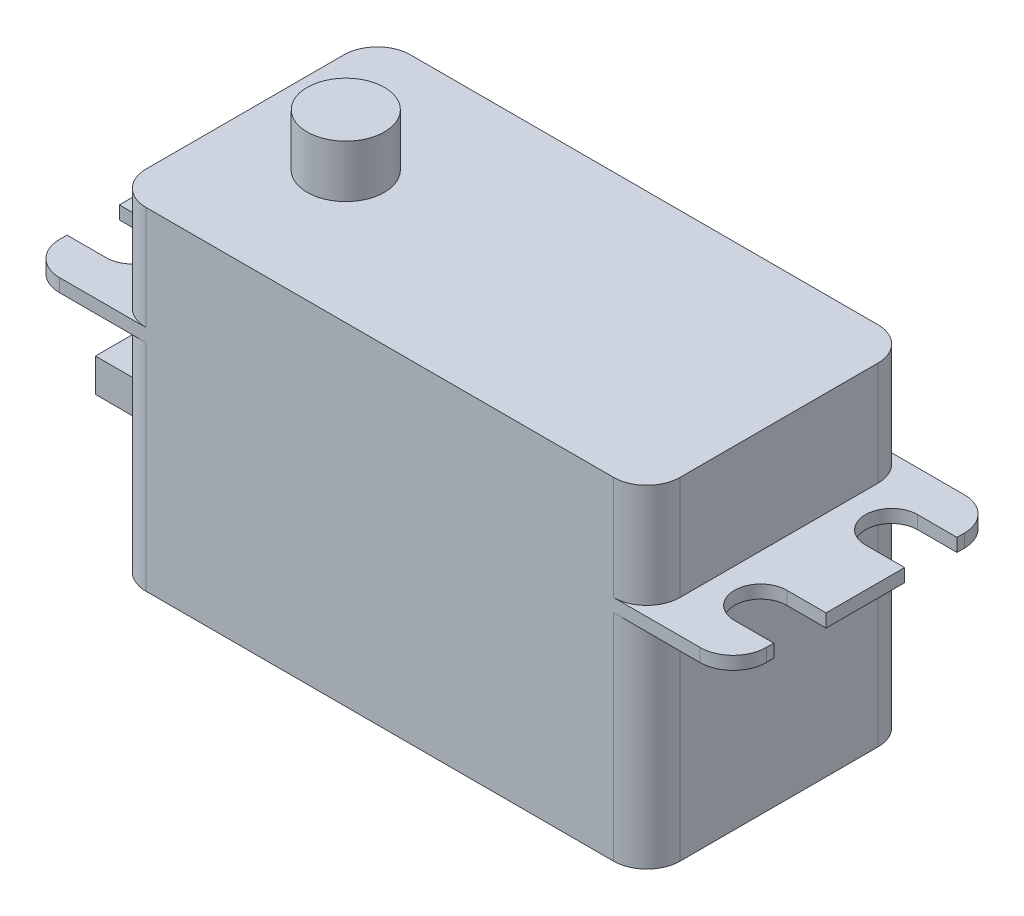
SolidWorks part; units mm, degrees
ref_plane "Front Plane" through (0, 0, 0) normal (0, 0, 1) x (1, 0, 0)
ref_plane "Top Plane" through (0, 0, 0) normal (0, 1, 0) x (1, 0, 0)
ref_plane "Right Plane" through (0, 0, 0) normal (1, 0, 0) x (0, 0, -1)
sketch "Sketch1" plane through (0, 0, 0) normal (0, 1, 0) x (1, 0, 0)
  line L0 (-16.17, 0) -> (16.17, 0) construction
  line L1 (-24.46, -10.1) -> (24.46, -10.1)
  line L2 (-27, -7.56) -> (-27, 7.56)
  line L3 (-24.46, 10.1) -> (24.46, 10.1)
  line L4 (27, -7.56) -> (27, 7.56)
  line L5 (-27, -10.1) -> (27, 10.1) construction
  line L6 (-27, 10.1) -> (27, -10.1) construction
  line L7 (0, -11.11) -> (0, 11.11) construction
  line L8 (24, 3) -> (27, 3)
  line L9 (24, 7) -> (27, 7)
  line L10 (27, 7) -> (27, 3)
  line L11 (24, -3) -> (27, -3)
  line L12 (24, -7) -> (27, -7)
  line L13 (27, -7) -> (27, -3)
  line L14 (-24, 7) -> (-27, 7)
  line L15 (-24, 3) -> (-27, 3)
  line L16 (-27, 3) -> (-27, 7)
  line L17 (-24, -7) -> (-27, -7)
  line L18 (-24, -3) -> (-27, -3)
  line L19 (-27, -3) -> (-27, -7)
  arc A0 (24, 7) -> (24, 3) centre (24, 5) ccw
  arc A1 (24, -7) -> (24, -3) centre (24, -5) cw
  arc A2 (-24, -7) -> (-24, -3) centre (-24, -5) ccw
  arc A3 (-24, 7) -> (-24, 3) centre (-24, 5) cw
  arc A4 (-24.46, -10.1) -> (-27, -7.56) centre (-24.46, -7.56) cw
  arc A5 (24.46, -10.1) -> (27, -7.56) centre (24.46, -7.56) ccw
  arc A6 (24.46, 10.1) -> (27, 7.56) centre (24.46, 7.56) cw
  arc A7 (-27, 7.56) -> (-24.46, 10.1) centre (-24.46, 7.56) cw
  point P0 (0, 0)
  dimension "D3" = 4
  dimension "D6" = 2.54
  dimension "D1" = 54
  dimension "D2" = 20.2
  dimension "D4" = 48
  dimension "D5" = 10
extrude "Boss-Extrude1" add sketch "Sketch1" along normal blind 1 contours A7 L2 L14 A3 L15 L18 A2 L17 A4 L1 A5 L4 L12 A1 L11 L8 A0 L9 A6 L3 region at (0, 0, 0)
sketch "Sketch3" plane through (0, 1, 0) normal (0, 1, 0) x (1, 0, 0)
  line L1 (-17.86, -10.1) -> (17.86, -10.1)
  line L2 (-20.4, -7.56) -> (-20.4, 7.56)
  line L3 (-17.86, 10.1) -> (17.86, 10.1)
  line L4 (20.4, -7.56) -> (20.4, 7.56)
  line L5 (-20.4, -10.1) -> (20.4, 10.1) construction
  line L6 (-20.4, 10.1) -> (20.4, -10.1) construction
  arc A0 (-17.86, -10.1) -> (-20.4, -7.56) centre (-17.86, -7.56) cw
  arc A1 (17.86, -10.1) -> (20.4, -7.56) centre (17.86, -7.56) ccw
  arc A2 (17.86, 10.1) -> (20.4, 7.56) centre (17.86, 7.56) cw
  arc A3 (-20.4, 7.56) -> (-17.86, 10.1) centre (-17.86, 7.56) cw
  point P0 (0, 0)
  dimension "D3" = 2.54
  dimension "D1" = 40.8
  dimension "D2" = 20.2
extrude "Boss-Extrude2" add sketch "Sketch3" along normal blind 7.95
sketch "Sketch4" plane through (0, 0, 0) normal (0, -1, 0) x (1, 0, 0)
  line L1 (-17.86, -10.1) -> (17.86, -10.1)
  line L2 (-20.4, -7.56) -> (-20.4, 7.56)
  line L3 (-17.86, 10.1) -> (17.86, 10.1)
  line L4 (20.4, -7.56) -> (20.4, 7.56)
  line L5 (-20.4, -10.1) -> (20.4, 10.1) construction
  line L6 (-20.4, 10.1) -> (20.4, -10.1) construction
  arc A0 (-17.86, -10.1) -> (-20.4, -7.56) centre (-17.86, -7.56) cw
  arc A1 (17.86, -10.1) -> (20.4, -7.56) centre (17.86, -7.56) ccw
  arc A2 (17.86, 10.1) -> (20.4, 7.56) centre (17.86, 7.56) cw
  arc A3 (-20.4, 7.56) -> (-17.86, 10.1) centre (-17.86, 7.56) cw
  point P0 (0, 0)
  dimension "D3" = 2.54
  dimension "D1" = 20.2
  dimension "D2" = 40.8
extrude "Boss-Extrude3" add sketch "Sketch4" along normal blind 16.45
sketch "Sketch5" plane through (-20.4, 0, 0) normal (-1, 0, 0) x (0, 0, 1)
  line L0 (-0.8843, -9.5287) -> (-0.8843, -11.2259)
  line L1 (-3.81, -11.6473) -> (3.81, -11.6473)
  line L2 (-3.81, -11.6473) -> (-3.81, -9.1073)
  line L3 (-3.81, -9.1073) -> (3.81, -9.1073)
  line L4 (3.81, -11.6473) -> (3.81, -9.1073)
  line L5 (-3.4243, -9.5287) -> (-1.6557, -9.5287)
  line L6 (-3.4243, -9.5287) -> (-3.4243, -11.2259)
  line L7 (-3.4243, -11.2259) -> (-1.6557, -11.2259)
  line L8 (-1.6557, -9.5287) -> (-1.6557, -11.2259)
  line L9 (-0.8843, -9.5287) -> (0.8843, -9.5287)
  line L10 (0.8843, -9.5287) -> (0.8843, -11.2259)
  line L11 (-0.8843, -11.2259) -> (0.8843, -11.2259)
  line L12 (1.6557, -9.5287) -> (1.6557, -11.2259)
  line L13 (1.6557, -9.5287) -> (3.4243, -9.5287)
  line L14 (3.4243, -9.5287) -> (3.4243, -11.2259)
  line L15 (1.6557, -11.2259) -> (3.4243, -11.2259)
  point P8 (0, -11.6473)
  point P18 (-3.4243, -10.3773)
  point P19 (-3.81, -10.3773)
  point P20 (0, -11.2259)
  dimension "D2" = 2.54
  dimension "D3" = 2.54
  dimension "D4" = 7.62
  dimension "D1" = 3
extrude "Boss-Extrude4" add sketch "Sketch5" along normal blind 7.62
sketch "Sketch6" plane through (0, 8.95, 0) normal (0, 1, 0) x (1, 0, 0)
  circle A0 centre (-12.7, 0) radius 2.95
  dimension "D1" = 5.9
  dimension "D2" = 12.7
extrude "Boss-Extrude5" add sketch "Sketch6" along normal blind 4
other "CPoint1" parameters "Diameter"=25.4, "StubLength"=38.1
ref_axis "Axis1" through (-38.02, -11.2259, -3.4243) along (1, 0, 0)
other "CPoint2" parameters "Diameter"=25.4, "StubLength"=38.1
ref_axis "Axis2" through (-38.02, -11.2259, -0.8843) along (1, 0, 0)
other "CPoint3" parameters "Diameter"=25.4, "StubLength"=38.1
ref_axis "Axis3" through (-38.02, -11.2259, 1.6557) along (1, 0, 0)
equation "\"Bodytube_OD\"= 6.17in"
equation "\"Bodytube_ID\"= 5.998in"
equation "\"Motor_OD\"= 4in"
equation "\"Fwd_Tube_Length\"= 40in"
equation "\"Mid_Tube_Length\"= 1in"
equation "\"Aft_Section_Length\"= 39in"
equation "\"AB_Coupler_OD_Length\"= 1in"
equation "\"AB_Coupling_Section_Length\"= 0.375in"
equation "\"AB_Coupler_Length\"= \"AB_Coupler_OD_Length\" + \"AB_Coupling_Section_Length\" * 2"
equation "\"Cutout_Angle\"= 80"
equation "\"AB_Paddle_Height\"= 0.375in"
equation "\"AB_Coupler_Num_Screws\"= 4"
equation "\"Num_Cutouts\"= 3"
equation "\"AB_Coupler_OD\"= 6.17in"
equation "\"AB_Coupler_ID\"= 5.75in"
equation "\"AB_Coupler_Surface_Diameter\"= 5.998in"
equation "\"AB_Coupling_Screw_Diameter\"= 0.15748in"
equation "\"AB_Central_Bushing_Length\"= .4724in"
equation "\"Lead_Screw_Dist\"= 3.4in"
equation "\"Lead_Screw_Diam\"= 0.386in"
equation "\"Paddle_Pin_Offset\"= .25in"
equation "\"Paddle_Pin_Radius\"= 2.25in"
equation "\"Paddle_Gear_OD\"= 3.2in"
equation "\"Drive_Gear_OD\"= 1.7in"
equation "\"Fwd_BKHD_From_Top\"= 18in"
equation "\"Fin_Thickness\"= .118in"
equation "\"Guiderail_Cutout_Diameter\"= 1.5in"
equation "\"DB9_Hole_Dist\"= 25mm"
equation "\"Airbrakes_Wire_Hole_Dia\"= .25in"
equation "\"Airbrakes_Wire_Hole_Dist\"= 1.1in"
equation "\"Servo_Gear_Offset\"= 0.5in"
equation "\"D2@Sketch6\"=\"Servo_Gear_Offset\""
